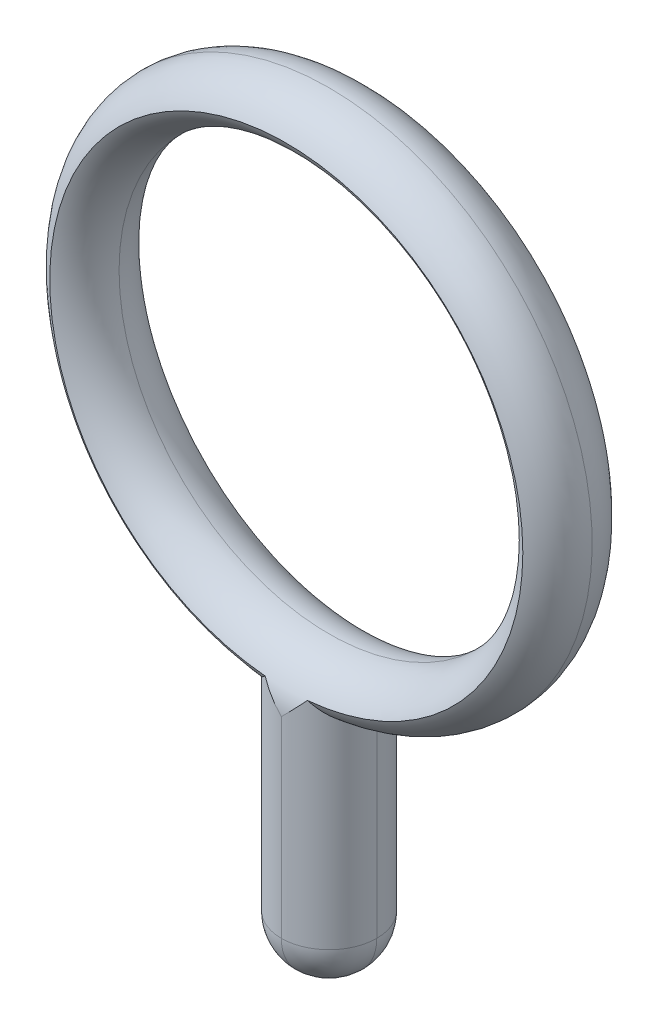
SolidWorks part; units mm, degrees
ref_plane "Front Plane" through (0, 0, 0) normal (0, 0, 1) x (1, 0, 0)
ref_plane "Top Plane" through (0, 0, 0) normal (0, 1, 0) x (1, 0, 0)
ref_plane "Right Plane" through (0, 0, 0) normal (1, 0, 0) x (0, 0, -1)
sketch "Sketch1" plane through (0, 0, 0) normal (0, 0, 1) x (1, 0, 0)
  line L0 (0, 0) -> (0, -13.0285) construction
  line L4 (0, -55) -> (0, 55) construction
  line L5 (-1.25, -13.0285) -> (1.25, -13.0285)
  line L6 (1.25, -13.0285) -> (1.25, -6.7765)
  line L7 (-1.25, -13.0285) -> (-1.25, -6.7765)
  circle A0 centre (0, 0) radius 5.5
  arc A1 (1.25, -6.7765) -> (-1.25, -6.7765) centre (0, 0) ccw
  point P10 (0, -13.0285)
  dimension "D1" = 2.5
extrude "Boss-Extrude1" add sketch "Sketch1" along normal blind 2.5
fillet "Fillet1" radius 1.2499 12 edges at (5.5, 0, 0) (5.5, 0, 2.5) (1.25, -9.9025, 0) (0, 6.8909, 0) (-1.25, -9.9025, 0) (0, -13.0285, 0) (1.25, -9.9025, 2.5) (-1.25, -9.9025, 2.5) (0, -13.0285, 2.5) (1.25, -13.0285, 1.25) (-1.25, -13.0285, 1.25) (0, 6.8909, 2.5)
